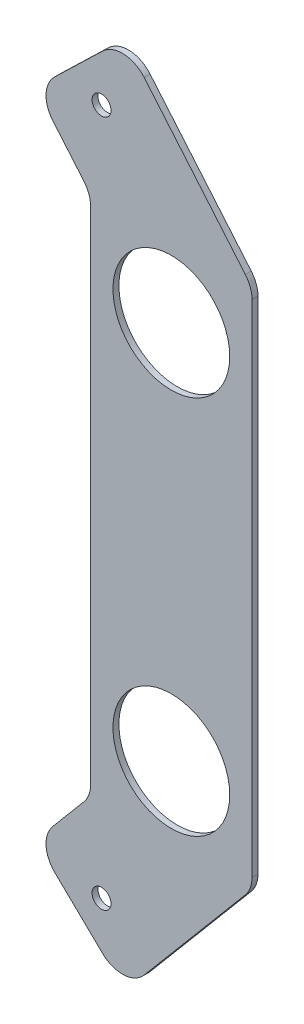
SolidWorks part; units mm, degrees
material "6061 Alloy"
ref_plane "Front Plane" through (0, 0, 0) normal (0, 0, 1) x (1, 0, 0)
ref_plane "Top Plane" through (0, 0, 0) normal (0, 1, 0) x (1, 0, 0)
ref_plane "Right Plane" through (0, 0, 0) normal (1, 0, 0) x (0, 0, -1)
sketch "Sketch1" plane through (0, 0, 0) normal (0, 0, 1) x (1, 0, 0)
  line L0 (0, 0) -> (0, -101.6) construction
  line L1 (21.59, -120.5575) -> (-21.59, -120.5575) construction
  line L2 (-8.89, 25.4) -> (8.89, 25.4) construction
  line L3 (-21.59, 12.7) -> (-21.59, -117.7751)
  line L5 (21.59, 12.7) -> (21.59, -117.7751)
  line L9 (-23.3829, -122.6853) -> (-31.7351, -132.597)
  line L10 (-36.322, 25.4) -> (20.828, 25.4) construction
  line L11 (-36.322, 25.4) -> (-36.322, -203.2) construction
  line L12 (-36.322, -203.2) -> (20.828, -203.2) construction
  line L13 (20.828, 25.4) -> (20.828, -203.2) construction
  line L14 (-31.203, -142.9869) -> (-18.3873, -155.3705)
  line L15 (-7.2652, -154.801) -> (19.7971, -122.6853)
  line L16 (-124.5546, -50.8) -> (107.4543, -50.8) construction
  line L17 (-7.2652, 53.201) -> (19.7971, 21.0853)
  line L18 (-31.203, 41.3869) -> (-18.3873, 53.7705)
  line L19 (-23.3829, 21.0853) -> (-31.7351, 30.997)
  line L20 (-21.59, 16.1751) -> (-21.59, 12.7)
  line L21 (21.59, 16.1751) -> (21.59, 12.7)
  circle A0 centre (0, 0) radius 38.1 construction
  circle A1 centre (0, -101.6) radius 38.1 construction
  circle A2 centre (0, 0) radius 15.621
  circle A3 centre (0, -101.6) radius 15.621
  arc A6 (20.828, 17.0329) -> (21.59, 12.7) centre (8.89, 12.7) cw construction
  arc A7 (-8.89, 25.4) -> (-21.59, 12.7) centre (-8.89, 12.7) ccw construction
  circle A10 centre (-18.6799, -142.7255) radius 2.54
  arc A11 (-31.7351, -132.597) -> (-31.203, -142.9869) centre (-25.908, -137.5071) ccw
  arc A12 (-18.3873, -155.3705) -> (-7.2652, -154.801) centre (-13.0923, -149.8908) ccw
  arc A13 (-23.3829, -122.6853) -> (-21.59, -117.7751) centre (-29.21, -117.7751) ccw
  arc A14 (19.7971, -122.6853) -> (21.59, -117.7751) centre (13.97, -117.7751) ccw
  circle A15 centre (-18.6799, 41.1255) radius 2.54
  arc A16 (19.7971, 21.0853) -> (21.59, 16.1751) centre (13.97, 16.1751) cw
  arc A17 (-18.3873, 53.7705) -> (-7.2652, 53.201) centre (-13.0923, 48.2908) cw
  arc A18 (-31.7351, 30.997) -> (-31.203, 41.3869) centre (-25.908, 35.9071) cw
  arc A19 (-23.3829, 21.0853) -> (-21.59, 16.1751) centre (-29.21, 16.1751) cw
  arc A20 (8.89, 25.4) -> (20.828, 17.0329) centre (8.89, 12.7) cw construction
  point P13 (-192.705, 39.2708)
  point P20 (21.59, 25.4)
  point P23 (-21.59, 25.4)
  point P31 (-36.322, -138.0404)
  dimension "D2" = 76.2
  dimension "D3" = 76.2
  dimension "D4" = 31.242
  dimension "D5" = 31.242
  dimension "D10" = 228.6
  dimension "D11" = 36.322
  dimension "D13" = 5.08
  dimension "D19" = 7.62
  dimension "D20" = 7.62
  dimension "D21" = 12.7
  dimension "D1" = 101.6
  dimension "D6" = 43.18
  dimension "D7" = 21.59
  dimension "D8" = 25.4
  dimension "D9" = 57.15
  dimension "D12" = 25.4
  dimension "D14" = 33.02
  dimension "D15" = 16.51
  dimension "D16" = 8.89
  dimension "D17" = 44.018
  dimension "D18" = 18.9575
  dimension "D22" = 50.8
extrude "Boss-Extrude1" add sketch "Sketch1" along normal blind 1.5875
